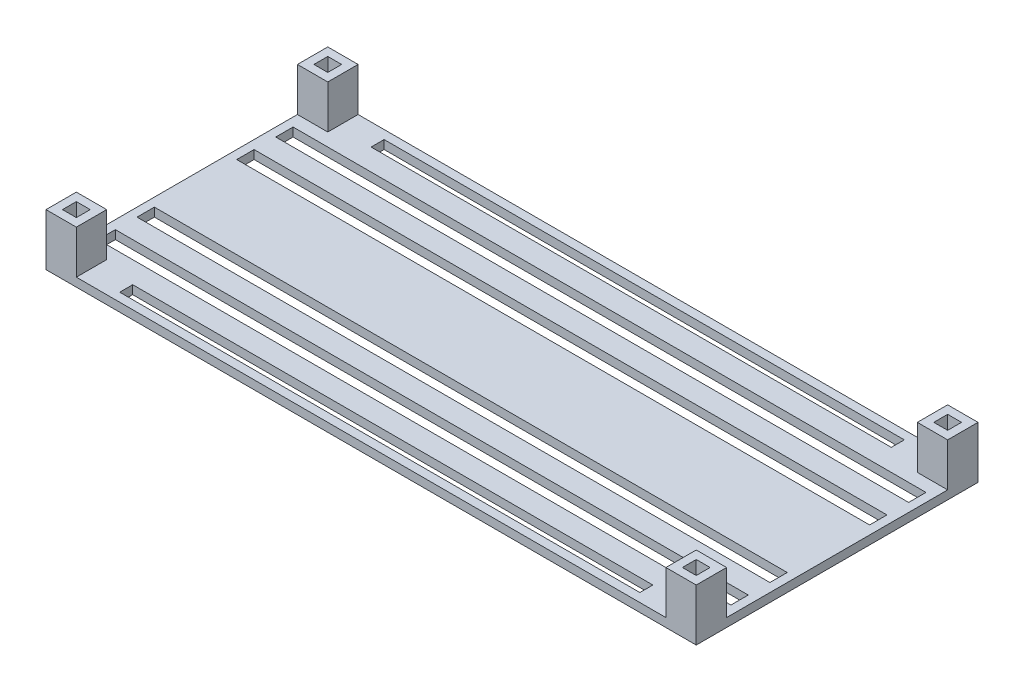
SolidWorks part; units mm, degrees
note: The reader was unsure of these and kept them because the rebuilt part matched: shared geometry of "Sketch2<3>".
ref_plane "Front" through (0, 0, 0) normal (0, 0, 1) x (1, 0, 0)
ref_plane "Top" through (0, 0, 0) normal (0, 1, 0) x (1, 0, 0)
ref_plane "Right" through (0, 0, 0) normal (1, 0, 0) x (0, 0, -1)
sketch "Sketch1" plane through (0, 0, 0) normal (0, 1, 0) x (1, 0, 0)
  line L1 (-75, -32.5) -> (75, -32.5)
  line L2 (-75, -32.5) -> (-75, 32.5)
  line L3 (-75, 32.5) -> (75, 32.5)
  line L4 (75, -32.5) -> (75, 32.5)
  line L5 (-75, -32.5) -> (75, 32.5) construction
  line L6 (-75, 32.5) -> (75, -32.5) construction
  point P0 (0, 0)
  dimension "D1" = 65
  dimension "D2" = 150
extrude "Boss-Extrude1" add sketch "Sketch1" along normal blind 2
sketch "Sketch2" plane through (0, 0, 0) normal (0, 1, 0) x (1, 0, 0)
  line L1 (70, 27.5) -> (73, 27.5)
  line L2 (70, 27.5) -> (70, 30.5)
  line L3 (70, 30.5) -> (73, 30.5)
  line L4 (73, 27.5) -> (73, 30.5)
  line L5 (70, 27.5) -> (73, 30.5) construction
  line L6 (70, 30.5) -> (73, 27.5) construction
  line L10 (75, -32.5) -> (75, 32.5)
  line L11 (75, 32.5) -> (-75, 32.5)
  line L12 (-75, 32.5) -> (-75, -32.5)
  line L13 (-75, -32.5) -> (75, -32.5)
  line L14 (75, -32.5) -> (75, 32.5) construction
  line L15 (75, 32.5) -> (-75, 32.5) construction
  line L16 (-75, 32.5) -> (-75, -32.5) construction
  line L17 (-75, -32.5) -> (75, -32.5) construction
  line L18 (0, 10.996) -> (0, -11.6042) construction
  line L19 (-16.954, 0) -> (16.954, 0) construction
  line L21 (-70, 30.5) -> (-73, 27.5) construction
  line L22 (-70, 27.5) -> (-73, 30.5) construction
  line L23 (-73, 27.5) -> (-73, 30.5)
  line L24 (-70, 30.5) -> (-73, 30.5)
  line L25 (-70, 27.5) -> (-70, 30.5)
  line L26 (-70, 27.5) -> (-73, 27.5)
  line L27 (-70, -27.5) -> (-73, -30.5) construction
  line L28 (-70, -30.5) -> (-73, -27.5) construction
  line L29 (-70, -27.5) -> (-73, -27.5)
  line L30 (-70, -27.5) -> (-70, -30.5)
  line L31 (-70, -30.5) -> (-73, -30.5)
  line L32 (-73, -27.5) -> (-73, -30.5)
  line L33 (70, -30.5) -> (73, -27.5) construction
  line L34 (70, -27.5) -> (73, -30.5) construction
  line L35 (73, -27.5) -> (73, -30.5)
  line L36 (70, -30.5) -> (73, -30.5)
  line L37 (70, -27.5) -> (70, -30.5)
  line L38 (70, -27.5) -> (73, -27.5)
  point P0 (71.5, 29)
  point P17 (-71.5, 29)
  point P22 (-71.5, -29)
  point P27 (0, 0)
  point P29 (71.5, -29)
  dimension "D1" = 3
  dimension "D2" = 0
  dimension "D3" = 2
  dimension "D4" = 2
extrude "Boss-Extrude2" add sketch "Sketch2" along normal blind 50 from surface at 2 starting at face at (0, 2, 0)
sketch "Sketch4" plane through (0, 2, 0) normal (0, 1, 0) x (1, 0, 0)
  line L0 (-73, 13.5) -> (-73, 9.5)
  line L1 (-60, 30.5) -> (60, 30.5)
  line L2 (-60, 30.5) -> (-60, 27.5)
  line L3 (-60, 27.5) -> (60, 27.5)
  line L4 (60, 30.5) -> (60, 27.5)
  line L5 (-60, 30.5) -> (60, 27.5) construction
  line L6 (-60, 27.5) -> (60, 30.5) construction
  line L7 (-73, 22.5) -> (73, 22.5)
  line L8 (-73, 22.5) -> (-73, 18.5)
  line L9 (-73, 18.5) -> (73, 18.5)
  line L10 (73, 27.5) -> (73, 30.5)
  line L11 (73, 30.5) -> (70, 30.5)
  line L12 (70, 30.5) -> (70, 27.5)
  line L13 (70, 27.5) -> (73, 27.5)
  line L14 (73, 27.5) -> (73, 30.5)
  line L15 (73, 30.5) -> (70, 30.5)
  line L16 (70, 30.5) -> (70, 27.5)
  line L17 (70, 27.5) -> (73, 27.5)
  line L18 (73, 22.5) -> (73, 18.5)
  line L19 (-73, 22.5) -> (73, 18.5) construction
  line L20 (-73, 18.5) -> (73, 22.5) construction
  line L21 (-73, 13.5) -> (73, 13.5)
  line L22 (73, 13.5) -> (73, 9.5)
  line L23 (-73, 9.5) -> (73, 9.5)
  line L24 (-8.1867, 0) -> (10.3388, 0) construction
  line L25 (-60, -27.5) -> (60, -27.5)
  line L26 (60, -30.5) -> (60, -27.5)
  line L27 (-60, -30.5) -> (60, -30.5)
  line L28 (-60, -30.5) -> (-60, -27.5)
  line L29 (-73, -18.5) -> (73, -18.5)
  line L30 (73, -22.5) -> (73, -18.5)
  line L31 (-73, -22.5) -> (73, -22.5)
  line L32 (-73, -22.5) -> (-73, -18.5)
  line L33 (-73, -13.5) -> (73, -13.5)
  line L34 (73, -13.5) -> (73, -9.5)
  line L35 (-73, -9.5) -> (73, -9.5)
  line L36 (-73, -13.5) -> (-73, -9.5)
  point P0 (0, 29)
  point P7 (70, 29)
  point P11 (0, 20.5)
  dimension "D2" = 120
  dimension "D3" = 5
  dimension "D4" = 4
  dimension "D1" = 0
  dimension "D5" = 2
extrude "Cut-Extrude2" cut sketch "Sketch4" against normal through all both and the other way through all contours L4 L1 L2 L3 | L18 L7 L8 L9 | L0 L23 L22 L21 | L36 L33 L34 L35 | L32 L31 L30 L29 | L28 L27 L26 L25
sketch "Sketch5" plane through (0, 2, 0) normal (0, 1, 0) x (1, 0, 0)
  line L4 (70, 27.5) -> (73, 27.5)
  line L5 (73, 27.5) -> (73, 30.5)
  line L6 (73, 30.5) -> (70, 30.5)
  line L7 (70, 30.5) -> (70, 27.5)
  line L8 (70, 27.5) -> (73, 27.5)
  line L9 (73, 27.5) -> (73, 30.5)
  line L10 (73, 30.5) -> (70, 30.5)
  line L11 (70, 30.5) -> (70, 27.5)
  line L12 (73, -30.5) -> (73, -27.5)
  line L13 (70, -30.5) -> (73, -30.5)
  line L14 (70, -27.5) -> (70, -30.5)
  line L15 (73, -27.5) -> (70, -27.5)
  line L16 (73, -30.5) -> (73, -27.5)
  line L17 (70, -30.5) -> (73, -30.5)
  line L18 (70, -27.5) -> (70, -30.5)
  line L19 (73, -27.5) -> (70, -27.5)
  line L20 (-70, -27.5) -> (-73, -27.5)
  line L21 (-73, -27.5) -> (-73, -30.5)
  line L22 (-73, -30.5) -> (-70, -30.5)
  line L23 (-70, -30.5) -> (-70, -27.5)
  line L24 (-70, -27.5) -> (-73, -27.5)
  line L25 (-73, -27.5) -> (-73, -30.5)
  line L26 (-73, -30.5) -> (-70, -30.5)
  line L27 (-70, -30.5) -> (-70, -27.5)
  line L28 (-73, 30.5) -> (-73, 27.5)
  line L29 (-73, 27.5) -> (-70, 27.5)
  line L30 (-70, 27.5) -> (-70, 30.5)
  line L31 (-70, 30.5) -> (-73, 30.5)
  line L32 (-73, 30.5) -> (-73, 27.5)
  line L33 (-73, 27.5) -> (-70, 27.5)
  line L34 (-70, 27.5) -> (-70, 30.5)
  line L35 (-70, 30.5) -> (-73, 30.5)
  line L36 (-11.2495, 0) -> (14.0688, 0) construction
  line L37 (0, 4.3586) -> (0, -3.6044) construction
  line L38 (-68, 25.5) -> (-75, 25.5)
  line L39 (-68, 32.5) -> (-68, 25.5)
  line L40 (75, 25.5) -> (75, 32.5)
  line L41 (75, 32.5) -> (68, 32.5)
  line L42 (68, 32.5) -> (68, 25.5)
  line L43 (68, 25.5) -> (75, 25.5)
  line L44 (75, 25.5) -> (75, 32.5)
  line L45 (75, 32.5) -> (68, 32.5)
  line L46 (68, 32.5) -> (68, 25.5)
  line L47 (68, 25.5) -> (75, 25.5)
  line L48 (-75, 32.5) -> (-68, 32.5)
  line L49 (-75, 25.5) -> (-75, 32.5)
  line L50 (68, -25.5) -> (75, -25.5)
  line L51 (68, -32.5) -> (68, -25.5)
  line L52 (75, -32.5) -> (68, -32.5)
  line L53 (75, -25.5) -> (75, -32.5)
  line L54 (-68, -32.5) -> (-68, -25.5)
  line L55 (-75, -32.5) -> (-68, -32.5)
  line L56 (-75, -25.5) -> (-75, -32.5)
  line L57 (-68, -25.5) -> (-75, -25.5)
  line L62 (-69.9, 27.4) -> (-73.1, 27.4)
  line L63 (-69.9, 30.6) -> (-69.9, 27.4)
  line L64 (-73.1, 30.6) -> (-69.9, 30.6)
  line L65 (-73.1, 27.4) -> (-73.1, 30.6)
  line L66 (73.1, 27.4) -> (73.1, 30.6)
  line L67 (73.1, 30.6) -> (69.9, 30.6)
  line L68 (69.9, 30.6) -> (69.9, 27.4)
  line L69 (69.9, 27.4) -> (73.1, 27.4)
  line L70 (73.1, 27.4) -> (73.1, 30.6)
  line L71 (73.1, 30.6) -> (69.9, 30.6)
  line L72 (69.9, 30.6) -> (69.9, 27.4)
  line L73 (69.9, 27.4) -> (73.1, 27.4)
  line L74 (69.9, -27.4) -> (73.1, -27.4)
  line L75 (69.9, -30.6) -> (69.9, -27.4)
  line L76 (73.1, -30.6) -> (69.9, -30.6)
  line L77 (73.1, -27.4) -> (73.1, -30.6)
  line L78 (-69.9, -30.6) -> (-69.9, -27.4)
  line L79 (-73.1, -30.6) -> (-69.9, -30.6)
  line L80 (-73.1, -27.4) -> (-73.1, -30.6)
  line L81 (-69.9, -27.4) -> (-73.1, -27.4)
  point P29 (0, 0)
  line M47 (75, -32.5) -> (75, 32.5)
  line M48 (75, 32.5) -> (-75, 32.5)
  line M49 (-75, 32.5) -> (-75, -32.5)
  line M50 (-75, -32.5) -> (75, -32.5)
  dimension "D1" = 0
  dimension "D2" = 0
  dimension "D3" = 0
  dimension "D4" = 0
  dimension "D5" = 2
  dimension "D6" = 0.1
extrude "Boss-Extrude3" add sketch "Sketch5" along normal blind 50 contours L46 L47 L73 L72 L71 L70 M47 M48 | L51 L50 L74 L77 L76 L75 M50 M47 | L54 L57 L81 L78 L79 L80 M49 M50 | L39 L38 L62 L65 L64 L63 M48 M49
extrude "Cut-Extrude3" cut sketch "Sketch2<3>" against normal up to next and the other way through all from surface
sketch "Sketch2<3>" plane through (0, 0, 0) normal (0, 1, 0) x (1, 0, 0) same geometry as "Sketch2"
sketch "Sketch6" plane through (0, 0, 0) normal (0, 0, 1) x (1, 0, 0)
  line L0 (-68, 2) -> (68, 2) construction
  line L1 (-91.3062, 64.9095) -> (91.4721, 64.9095)
  line L2 (-91.3062, 64.9095) -> (-91.3062, 12)
  line L3 (-91.3062, 12) -> (91.4721, 12)
  line L4 (91.4721, 64.9095) -> (91.4721, 12)
  dimension "D1" = 10
extrude "Cut-Extrude4" cut sketch "Sketch6" against normal through all both and the other way through all
